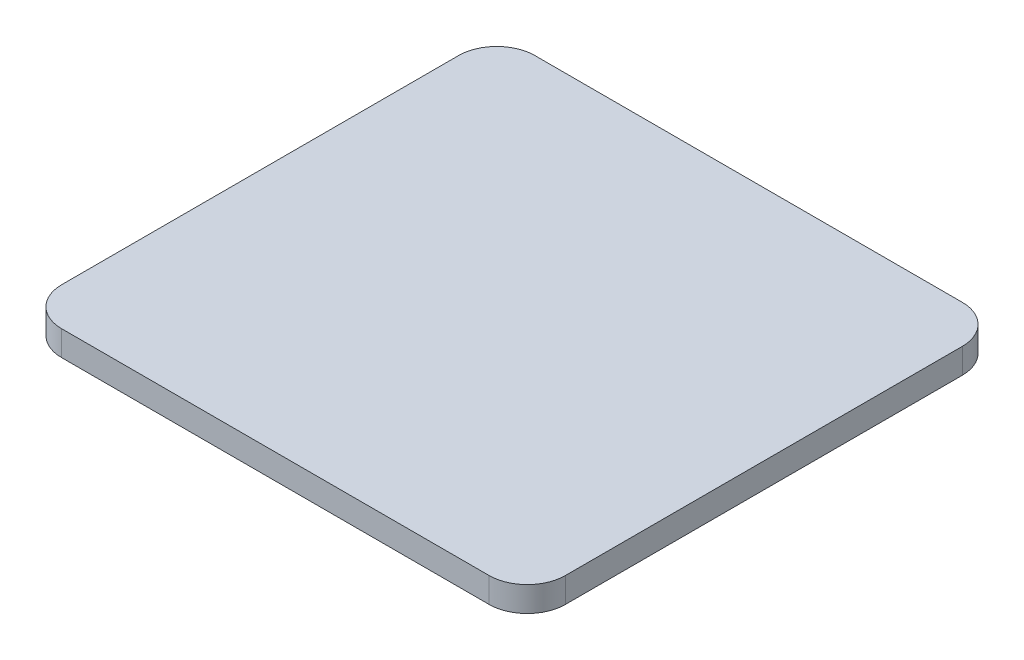
SolidWorks part; units mm, degrees
ref_plane "Front Plane" through (0, 0, 0) normal (0, 0, 1) x (1, 0, 0)
ref_plane "Top Plane" through (0, 0, 0) normal (0, 1, 0) x (1, 0, 0)
ref_plane "Right Plane" through (0, 0, 0) normal (1, 0, 0) x (0, 0, -1)
sketch "Sketch1" plane through (0, 0, 0) normal (0, 1, 0) x (1, 0, 0)
  line L0 (-21.6, 20.2) -> (-21.6, 21.7) construction
  line L1 (19.6, 20.2) -> (-19.6, 20.2)
  line L2 (21.6, 18.2) -> (21.6, -18.2)
  line L3 (19.6, -20.2) -> (-19.6, -20.2)
  line L4 (-21.6, 18.2) -> (-21.6, -18.2)
  line L5 (21.6, 20.2) -> (-21.6, -20.2) construction
  line L6 (21.6, -20.2) -> (-21.6, 20.2) construction
  line L7 (23.1, -21.7) -> (-23.1, -21.7)
  line L8 (23.1, -21.7) -> (23.1, 21.7)
  line L9 (23.1, 21.7) -> (-23.1, 21.7)
  line L10 (-23.1, -21.7) -> (-23.1, 21.7)
  line L11 (23.1, -21.7) -> (-23.1, 21.7) construction
  line L12 (23.1, 21.7) -> (-23.1, -21.7) construction
  line L13 (-21.6, 20.2) -> (-23.1, 20.2) construction
  arc A0 (-19.6, -20.2) -> (-21.6, -18.2) centre (-19.6, -18.2) cw
  arc A1 (21.6, -18.2) -> (19.6, -20.2) centre (19.6, -18.2) cw
  arc A2 (19.6, 20.2) -> (21.6, 18.2) centre (19.6, 18.2) cw
  arc A3 (-19.6, 20.2) -> (-21.6, 18.2) centre (-19.6, 18.2) ccw
  circle A4 centre (-19.6, 18.2) radius 3.5
  circle A5 centre (19.6, 18.2) radius 3.5
  circle A6 centre (19.6, -18.2) radius 3.5
  circle A7 centre (-19.6, -18.2) radius 3.5
  point P0 (0, 0)
  point P6 (0, 0)
  dimension "D4" = 2
  dimension "D1" = 43.2
  dimension "D2" = 40.4
  dimension "D3" = 1.5
extrude "Boss-Extrude1" add sketch "Sketch1" along normal blind 1.3 contours L1 A4 L4 A3 | A7 L4 A4 L10 | A7 L3 A0 L4 | A7 L7 A6 L3 | A6 L2 A1 L3 | A6 L8 A5 L2 | L2 A5 L1 A2 | A5 L9 A4 L1 region at (18.1639, 0, -20.2901) region at (0, 0, -20.9657) region at (-18.1639, 0, -20.2901) region at (22.3671, 0, 0) region at (22.6225, 0, 16.6215) region at (-22.3671, 0, 0) region at (0, 0, 20.9657) region at (-21.6901, 0, 16.7639)
sketch "Sketch2" plane through (0, 1.3, 0) normal (0, 1, 0) x (1, 0, 0)
  line L4 (-19.6, -21.7) -> (19.6, -21.7)
  line L5 (23.1, -18.2) -> (23.1, 18.2)
  line L6 (19.6, 21.7) -> (-19.6, 21.7)
  line L7 (-23.1, 18.2) -> (-23.1, -18.2)
  line L8 (-19.6, -21.7) -> (19.6, -21.7)
  line L9 (23.1, -18.2) -> (23.1, 18.2)
  line L10 (19.6, 21.7) -> (-19.6, 21.7)
  line L11 (-23.1, 18.2) -> (-23.1, -18.2)
  arc A4 (19.6, -21.7) -> (23.1, -18.2) centre (19.6, -18.2) ccw
  arc A5 (23.1, 18.2) -> (19.6, 21.7) centre (19.6, 18.2) ccw
  arc A6 (-19.6, 21.7) -> (-23.1, 18.2) centre (-19.6, 18.2) ccw
  arc A7 (-23.1, -18.2) -> (-19.6, -21.7) centre (-19.6, -18.2) ccw
  arc A8 (19.6, -21.7) -> (23.1, -18.2) centre (19.6, -18.2) ccw
  arc A9 (23.1, 18.2) -> (19.6, 21.7) centre (19.6, 18.2) ccw
  arc A10 (-19.6, 21.7) -> (-23.1, 18.2) centre (-19.6, 18.2) ccw
  arc A11 (-23.1, -18.2) -> (-19.6, -21.7) centre (-19.6, -18.2) ccw
  dimension "D1" = 0
extrude "Boss-Extrude2" add sketch "Sketch2" along normal blind 1
sketch "Sketch3" plane through (0, 1.3, 0) normal (0, -1, 0) x (1, 0, 0)
  line L0 (-23.1, 0) -> (23.1, 0) construction
  line L1 (-23.1, 18.2) -> (-23.1, -18.2) construction
  line L2 (23.1, 18.2) -> (23.1, -18.2) construction
  line L3 (-23.1, 10.85) -> (23.1, 10.85) construction
  line L4 (0, 10.85) -> (0, 21.7) construction
  line L5 (19.6, 21.7) -> (-19.6, 21.7) construction
  line L6 (0, 10.85) -> (0, 0) construction
  line L7 (-23.1, -10.85) -> (23.1, -10.85) construction
  line L8 (0, 0) -> (4.1348, 4.1348) construction
  line L9 (10.85, -23.1) -> (10.85, 23.1) construction
  line L10 (-10.85, -23.1) -> (-10.85, 23.1) construction
  line L11 (-21.6, -18.2) -> (-21.6, 18.2) construction
  line L12 (-21.6, -18.2) -> (-21.6, 18.2) construction
  line L13 (19.6, -20.2) -> (-19.6, -20.2) construction
  line L14 (21.6, -18.2) -> (21.6, 18.2) construction
  line L15 (19.6, 20.2) -> (-19.6, 20.2) construction
  line L16 (19.6, 20.2) -> (-19.6, 20.2) construction
  circle A0 centre (-21.6, 10.85) radius 0.4
  circle A1 centre (-21.6, 0) radius 0.4
  circle A2 centre (-21.6, -10.85) radius 0.4
  circle A3 centre (-10.85, -20.2) radius 0.4
  circle A4 centre (10.85, -20.2) radius 0.4
  circle A5 centre (21.6, -10.85) radius 0.4
  circle A6 centre (21.6, 0) radius 0.4
  circle A7 centre (21.6, 10.85) radius 0.4
  circle A8 centre (10.85, 20.2) radius 0.4
  circle A9 centre (0, 20.2) radius 0.4
  circle A10 centre (-10.85, 20.2) radius 0.4
  point P56 (-21.6, 0)
  point P57 (21.6, -10.85)
  dimension "D2" = 0.8
  dimension "D1" = 45
extrude "Boss-Extrude3" add sketch "Sketch3" along normal up to surface (1.3 mm away) up to face at (0, 0, 0)
